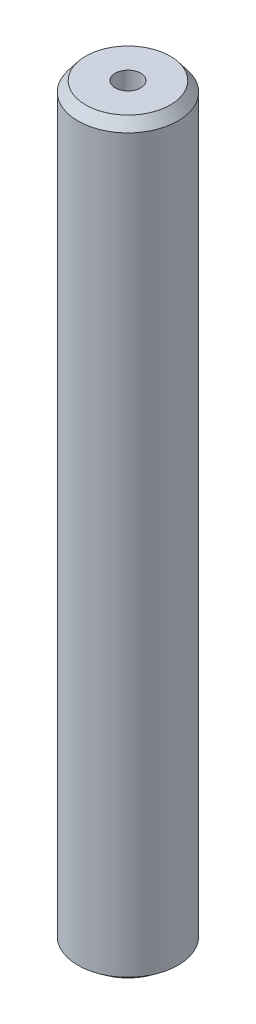
SolidWorks part; units mm, degrees
ref_plane "Front Plane" through (0, 0, 0) normal (0, 0, 1) x (1, 0, 0)
ref_plane "Top Plane" through (0, 0, 0) normal (0, 1, 0) x (1, 0, 0)
ref_plane "Right Plane" through (0, 0, 0) normal (1, 0, 0) x (0, 0, -1)
sketch "Sketch1" plane through (0, 0, 0) normal (0, 1, 0) x (1, 0, 0)
  circle A0 centre (0, 0) radius 5
  dimension "SHAFT_OD" = 10
extrude "Boss-Extrude1" add sketch "Sketch1" along normal blind 74.8395
sketch "Sketch2" plane through (0, 0, 0) normal (0, 1, 0) x (1, 0, 0)
  circle A0 centre (0, 0) radius 1.2749
  dimension "BORE_D" = 2.5497
extrude "Cut-Extrude1" cut sketch "Sketch2" along normal through all
chamfer "Chamfer1" distance 0.9995 angle 37.68 2 edges at (0, 74.8395, 5) (0, 0, 5) first distance on face at (0, 74.8395, 5) first distance on face at (0, 0, 1.2749)
